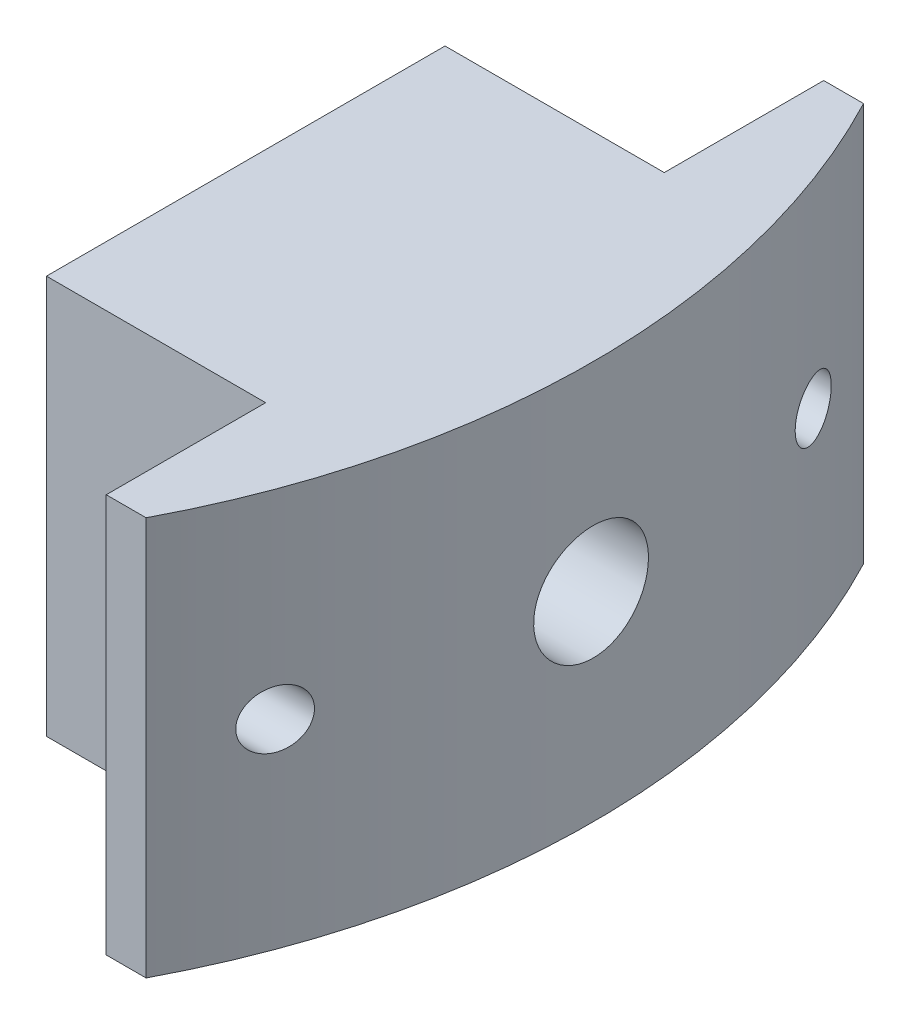
SolidWorks part; units mm, degrees
material "Plain Carbon Steel"
ref_plane "Front Plane" through (0, 0, 0) normal (0, 0, 1) x (1, 0, 0)
ref_plane "Top Plane" through (0, 0, 0) normal (0, 1, 0) x (1, 0, 0)
ref_plane "Right Plane" through (0, 0, 0) normal (1, 0, 0) x (0, 0, -1)
sketch "Sketch2" plane through (0, 0, 0) normal (0, 1, 0) x (1, 0, 0)
  line L0 (43.5809, 22.86) -> (43.5809, -22.86)
  line L1 (41.0409, 12.7) -> (41.0409, -12.7)
  line L2 (43.5809, 22.86) -> (41.0409, 22.86)
  line L3 (43.5809, 22.86) -> (43.5809, -22.86)
  line L4 (43.5809, -22.86) -> (41.0409, -22.86)
  line L5 (41.0409, 22.86) -> (41.0409, -22.86)
  line L6 (41.0409, 12.7) -> (27.0709, 12.7)
  line L11 (27.0709, 12.7) -> (27.0709, -12.7)
  line L12 (27.0709, -12.7) -> (41.0409, -12.7)
  line L13 (0, 0) -> (29.3279, 0) construction
  line L14 (0, 0) -> (47.5356, -12.7371) construction
  arc A0 (43.5809, -22.86) -> (43.5809, 22.86) centre (0, 0) ccw
  point P9 (41.0409, 0)
  dimension "D1" = 49.2125
  dimension "D2" = 45.72
  dimension "D3" = 2.54
  dimension "D4" = 25.4
  dimension "D5" = 13.97
  dimension "D6" = 15
extrude "Boss-Extrude1" add sketch "Sketch2" along normal blind 25.4 contours L11 L12 L1 L6 | L2 L5 L1 L4 L0 | L0 A0 | L0 A0 region at (45.8449, 0, 0) region at (42.3109, 0, 0) region at (34.0559, 0, 0)
ref_plane "Plane1" through (49.2125, 0, 0) normal (1, 0, 0) x (0, 0, -1)
sketch "Sketch4" plane through (27.0709, 0, 0) normal (-1, 0, 0) x (0, 0, 1)
  line L4 (-12.7, 0) -> (12.7, 25.4) construction
  line L5 (-12.7, 0) -> (12.7, 0) construction
  line L6 (-12.7, 25.4) -> (-12.7, 0) construction
  line L7 (-12.7, 25.4) -> (12.7, 0) construction
  line L8 (12.7, 25.4) -> (12.7, 0) construction
  line L9 (12.7, 25.4) -> (12.7, 0) construction
  circle A0 centre (0, 12.7) radius 3.81
  circle A1 centre (0, 12.7) radius 1.27
  point P15 (0, 12.7)
  dimension "D1" = 7.62
  dimension "D2" = 2.54
extrude "Cut-Extrude2" cut sketch "Sketch4" against normal up to next contours A1
sketch "Sketch11" plane through (41.0409, 0, 0) normal (-1, 0, 0) x (0, 0, 1)
  circle A2 centre (0, 12.7) radius 3.6576
  dimension "D3" = 7.3152
extrude "Cut-Extrude4" cut sketch "Sketch11" along normal blind 12.7 from surface contours A2 starting at plane "Plane1"
sketch "Sketch13" plane through (49.2125, 0, 0) normal (1, 0, 0) x (0, 0, -1)
  line L1 (-6.2992, 12.7) -> (-7.6327, 12.7) construction
  line L2 (-6.2992, 12.7) -> (-4.9657, 12.7) construction
  line L4 (0, 12.7) -> (-22.86, 12.7) construction
  line L5 (-22.86, 25.4) -> (-22.86, 0) construction
  circle A0 centre (0, 12.7) radius 4.9657
  circle A1 centre (0, 12.7) radius 7.6327
  circle A2 centre (0, 12.7) radius 6.2992 construction
  dimension "D1" = 12.5984
  dimension "D2" = 2.667
wrap "Wrap3" [suppressed] sketch "Sketch13" source sketch "Sketch13" thickness 1.3208 parameters "D1"=1.3208
sketch "Sketch15" plane through (0, 0, 0) normal (1, 0, 0) x (0, 0, -1)
  line L0 (-22.86, 12.7) -> (22.86, 12.7) construction
  line L1 (0, 0) -> (0, 25.4) construction
  line L4 (-22.86, 0) -> (22.86, 0)
  line L5 (22.86, 0) -> (22.86, 25.4)
  line L6 (22.86, 25.4) -> (-22.86, 25.4)
  line L7 (-22.86, 25.4) -> (-22.86, 0)
  line L8 (-22.86, 0) -> (22.86, 0)
  line L9 (22.86, 0) -> (22.86, 25.4)
  line L10 (22.86, 25.4) -> (-22.86, 25.4)
  line L11 (-22.86, 25.4) -> (-22.86, 0)
  circle A0 centre (-17.145, 12.7) radius 1.8288
  circle A1 centre (17.145, 12.7) radius 1.8288
  dimension "D2" = 3.6576
  dimension "D3" = 5.715
extrude "Cut-Extrude5" cut sketch "Sketch15" along normal up to surface (46.7684 mm away) contours L0 A0 | A1 region at (0, 12.7, 17.145) region at (0, 12.7, -17.145) up to face at (49.0834, 13.5299, 3.5622)
equation "\"Middle Coupler Inner Daimeter\"= 3.875in"
equation "\"Middle Coupler  Wall Thickness\" = 0.25in"
equation "\"Middle Coupler Bottom Thickness\"= 0.2in"
equation "\"Bearing Rail Offset\"= 0.45in"
equation "\"3-56 UNF Tap\"= 0.089in"
equation "\"3-48 Tap\"= 0.079in"
equation "\"3-56 UNF Clearance\"= 0.104in"
equation "\"3-48 Clearance\" = 0.104in"
equation "\"Ball Bearing Distance\"= 0.03in"
equation "\"TCA Outer Diameter\" = 6in"
equation "\"Interstage Aeroframe Wall Thickness\" = 0.072in"
equation "\"Compression Spring OD\"= 0.42in"
equation "\"10-24 Tap\"= 0.157in"
equation "\"10-24 Clearance\"= 0.196in"
equation "\"Lower Stage Fuselage Wall Thickness\" = 0.25in"
equation "\"6-32 Tap\" = 0.107in"
equation "\"6-32 Clearance\" = 0.144"
equation "\"1/4-20 Tap\" = 0.201in"
equation "\"12-24 Tap\" = 0.177in"
equation "\"D1@Sketch2\"=\"Middle Coupler Inner Daimeter\"/2"
equation "\"D2@Sketch15\"=\"6-32 Clearance\""
